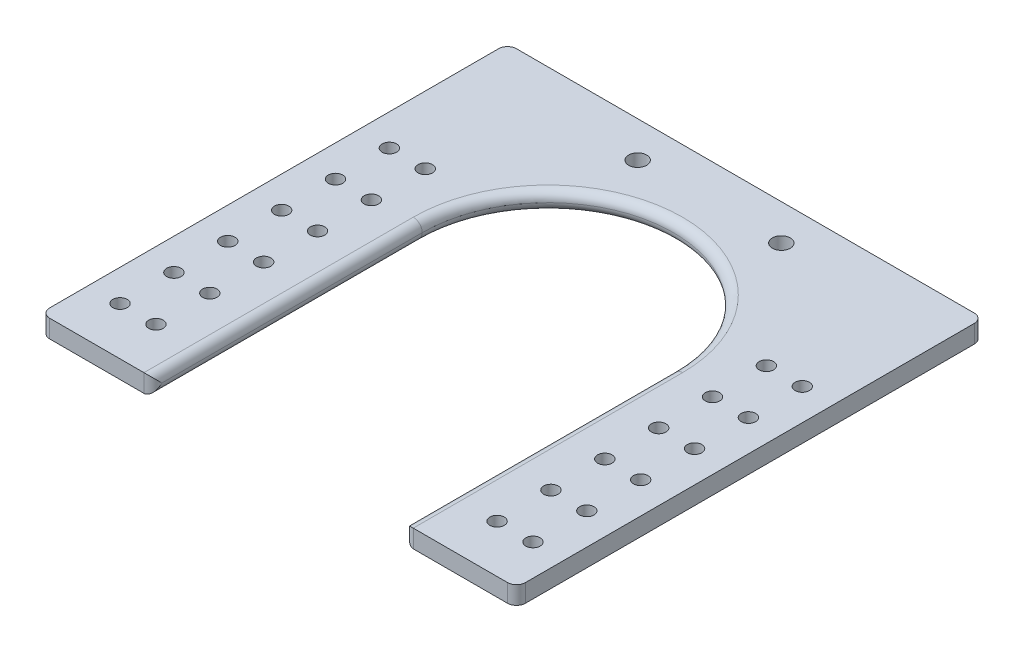
SolidWorks part; units mm, degrees
ref_plane "Front" through (0, 0, 0) normal (0, 0, 1) x (1, 0, 0)
ref_plane "Top" through (0, 0, 0) normal (0, 1, 0) x (1, 0, 0)
ref_plane "Right" through (0, 0, 0) normal (1, 0, 0) x (0, 0, -1)
sketch "Sketch1" plane through (0, 0, 0) normal (0, 1, 0) x (1, 0, 0)
  line L1 (-84.1375, -82.55) -> (84.1375, -82.55)
  line L2 (-84.1375, -82.55) -> (-84.1375, 82.55)
  line L3 (-84.1375, 82.55) -> (84.1375, 82.55)
  line L4 (84.1375, -82.55) -> (84.1375, 82.55)
  line L5 (-84.1375, -82.55) -> (84.1375, 82.55) construction
  line L6 (-84.1375, 82.55) -> (84.1375, -82.55) construction
  point P0 (0, 0)
  dimension "D1" = 168.275
  dimension "D2" = 165.1
extrude "Boss-Extrude1" add sketch "Sketch1" along normal mid plane 6.35 contours L3 L4 L1 L2
sketch "Sketch2" plane through (0, 3.175, 0) normal (0, 1, 0) x (1, 0, 0)
  line L0 (0, -50) -> (0, 50) construction
  line L1 (-84.1375, 82.55) -> (84.1375, 82.55) construction
  line L2 (44.45, 12.7) -> (44.45, -82.55)
  line L3 (-84.1375, -82.55) -> (84.1375, -82.55) construction
  line L4 (44.45, -82.55) -> (-44.45, -82.55)
  line L5 (-44.45, -82.55) -> (-44.45, 12.7)
  circle A0 centre (0, 12.7) radius 44.45
  point P4 (0, 57.15)
  line M2 (-84.1375, -82.55) -> (84.1375, -82.55)
  dimension "D2" = 88.9
  dimension "D1" = 25.4
extrude "Cut-Extrude1" cut sketch "Sketch2" against normal up to next contours A0 | A0 L5 L2 M2 region at (0, 3.175, -12.7) region at (0, 3.175, 51.5649)
sketch "Sketch3" plane through (0, 3.175, 0) normal (0, 1, 0) x (1, 0, 0)
  line L0 (-25.4, 69.85) -> (25.4, 69.85) construction
  line L1 (0, -50) -> (0, 50) construction
  line L2 (-84.1375, 82.55) -> (84.1375, 82.55) construction
  point P0 (-25.4, 69.85)
  point P1 (25.4, 69.85)
  point P4 (0, 69.85)
  dimension "D1" = 50.8
  dimension "D2" = 12.7
hole_wizard "1/4 (0.25) Diameter Hole1" positions "Sketch4" profile "Sketch6" hole size "1/4" standard "ANSI Inch"
sketch "Sketch4" plane through (0, 3.175, 0) normal (0, 1, 0) x (1, 0, 0)
  point P0 (-25.4, 69.85)
  point P3 (25.4, 69.85)
sketch "Sketch6" plane through (-25.4, 3.175, -69.85) normal (1, 0, 0) x (0, 0, 1)
  line L0 (0, 0) -> (0, 27.3077)
  line L1 (0, 27.3077) -> (3.175, 25.4)
  line L2 (3.175, 25.4) -> (3.175, 0)
  line L5 (3.175, 0) -> (0, 0)
  line L10 (0, 27.3077) -> (-3.175, 25.4) construction
  line L11 (0, -6.35) -> (0, 107.95) construction
  dimension "Hole Dia." = 6.35
  dimension "Hole Depth" = 25.4
  dimension "Drill Angle" = 118
sketch "Sketch7" plane through (0, 3.175, 0) normal (0, 1, 0) x (1, 0, 0)
  line L0 (-84.1375, -82.55) -> (-84.1375, 82.55) construction
  point P0 (-73.025, -65.6037)
  point P1 (-60.325, -65.6037)
  dimension "D1" = 11.1125
  dimension "D2" = 12.7
hole_wizard "1/4-20 Tapped Hole1" positions "Sketch8" profile "Sketch10" tap size "1/4-20" standard "ANSI Inch"
sketch "Sketch8" plane through (0, 3.175, 0) normal (0, 1, 0) x (1, 0, 0)
  point P0 (-73.025, -65.6037)
  point P3 (-60.325, -65.6037)
sketch "Sketch10" plane through (-73.025, 3.175, 65.6037) normal (1, 0, 0) x (0, 0, 1)
  line L0 (0, 0) -> (0, 26.9338)
  line L1 (0, 26.9338) -> (2.5527, 25.4)
  line L2 (2.5527, 25.4) -> (2.5527, 0)
  line L5 (2.5527, 0) -> (0, 0)
  line L10 (0, 26.9338) -> (-2.5527, 25.4) construction
  line L11 (0, -6.35) -> (0, 107.95) construction
  dimension "Tap Drill Dia." = 5.1054
  dimension "Tap Drill Depth" = 25.4
  dimension "Drill Angle" = 118
cosmetic thread "Hole Thread1" parameters "D1"=12.7, "D2"=6.35
cosmetic thread "Hole Thread2" parameters "D1"=12.7, "D2"=6.35
pattern_linear "LPattern1" count 6 spacing 19.05 along (0, 0, -1) of "1/4-20 Tapped Hole1"
cosmetic thread "Hole Thread3" parameters "D1"=12.7, "D2"=6.35
cosmetic thread "Hole Thread4" parameters "D1"=12.7, "D2"=6.35
cosmetic thread "Hole Thread5" parameters "D1"=12.7, "D2"=6.35
cosmetic thread "Hole Thread6" parameters "D1"=12.7, "D2"=6.35
cosmetic thread "Hole Thread7" parameters "D1"=12.7, "D2"=6.35
cosmetic thread "Hole Thread8" parameters "D1"=12.7, "D2"=6.35
cosmetic thread "Hole Thread9" parameters "D1"=12.7, "D2"=6.35
cosmetic thread "Hole Thread10" parameters "D1"=12.7, "D2"=6.35
cosmetic thread "Hole Thread11" parameters "D1"=12.7, "D2"=6.35
cosmetic thread "Hole Thread12" parameters "D1"=12.7, "D2"=6.35
mirror "Mirror1" about plane through (0, 0, 0) normal (1, 0, 0) of "LPattern1"
cosmetic thread "Hole Thread13" parameters "D1"=12.7, "D2"=6.35
cosmetic thread "Hole Thread14" parameters "D1"=12.7, "D2"=6.35
cosmetic thread "Hole Thread15" parameters "D1"=12.7, "D2"=6.35
cosmetic thread "Hole Thread16" parameters "D1"=12.7, "D2"=6.35
cosmetic thread "Hole Thread17" parameters "D1"=12.7, "D2"=6.35
cosmetic thread "Hole Thread18" parameters "D1"=12.7, "D2"=6.35
cosmetic thread "Hole Thread19" parameters "D1"=12.7, "D2"=6.35
cosmetic thread "Hole Thread20" parameters "D1"=12.7, "D2"=6.35
cosmetic thread "Hole Thread21" parameters "D1"=12.7, "D2"=6.35
cosmetic thread "Hole Thread22" parameters "D1"=12.7, "D2"=6.35
cosmetic thread "Hole Thread23" parameters "D1"=12.7, "D2"=6.35
cosmetic thread "Hole Thread24" parameters "D1"=12.7, "D2"=6.35
fillet "Fillet1" radius 3.175 10 edges at (-44.45, -3.175, 34.925) (0, -3.175, -57.15) (-44.45, 3.175, 34.925) (0, 3.175, -57.15) (44.45, -3.175, 34.925) (44.45, 3.175, 34.925) (84.1375, 0, 82.55) (44.45, 0, 82.55) (-84.1375, 0, 82.55) (-44.45, 0, 82.55)
fillet "Fillet2" radius 3.175 2 edges at (84.1375, 0, -82.55) (-84.1375, 0, -82.55)
